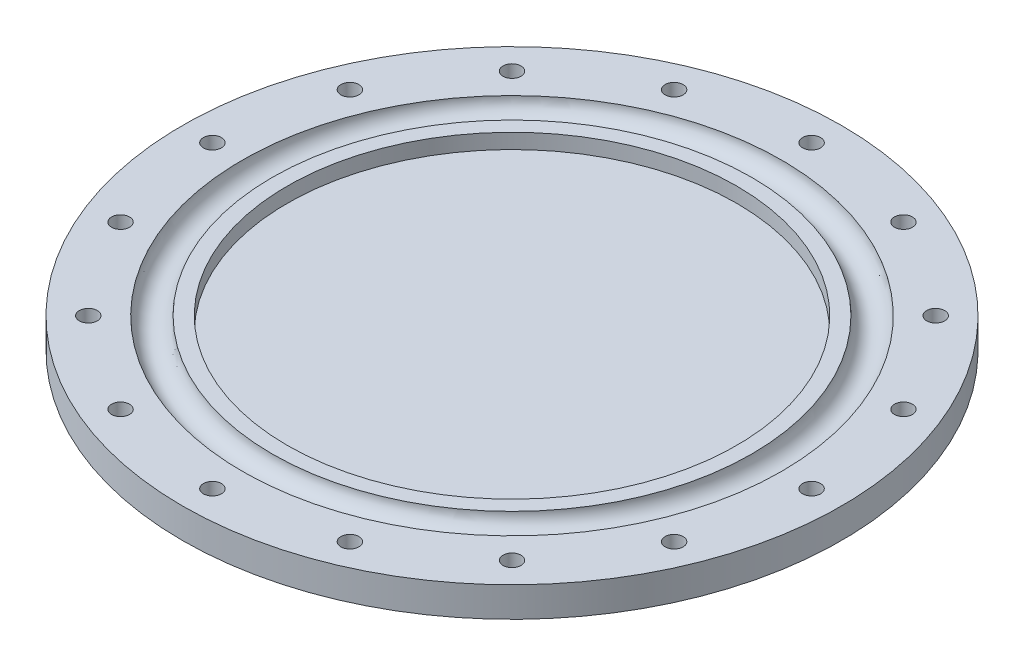
SolidWorks part; units mm, degrees
ref_plane "前视基准面" through (0, 0, 0) normal (0, 0, 1) x (1, 0, 0)
ref_plane "上视基准面" through (0, 0, 0) normal (0, 1, 0) x (1, 0, 0)
ref_plane "右视基准面" through (0, 0, 0) normal (1, 0, 0) x (0, 0, -1)
other "Configuration Table"
sketch "草图1" plane through (0, 0, 0) normal (0, 1, 0) x (1, 0, 0)
  circle A0 centre (0, 0) radius 75
  circle A1 centre (0, 0) radius 80
  circle A2 centre (0, 0) radius 90
  circle A3 centre (0, 0) radius 110
  circle A4 centre (0, 100) radius 3
  circle A5 centre (38.2683, 92.388) radius 3
  circle A6 centre (70.7107, 70.7107) radius 3
  circle A7 centre (92.388, 38.2683) radius 3
  circle A8 centre (100, 0) radius 3
  circle A9 centre (92.388, -38.2683) radius 3
  circle A10 centre (70.7107, -70.7107) radius 3
  circle A11 centre (38.2683, -92.388) radius 3
  circle A12 centre (0, -100) radius 3
  circle A13 centre (-38.2683, -92.388) radius 3
  circle A14 centre (-70.7107, -70.7107) radius 3
  circle A15 centre (-92.388, -38.2683) radius 3
  circle A16 centre (-100, 0) radius 3
  circle A17 centre (-92.388, 38.2683) radius 3
  circle A18 centre (-70.7107, 70.7107) radius 3
  circle A19 centre (-38.2683, 92.388) radius 3
  point P40 (0, 0)
  dimension "D1" = 150
  dimension "D2" = 160
  dimension "D3" = 180
  dimension "D4" = 220
  dimension "D5" = 6
  dimension "D6" = 100
  dimension "D7" = 16
extrude "凸台-拉伸1" add sketch "草图1" along normal blind 10 contours A3 A19 A18 A17 A16 A15 A14 A13 A12 A11 A10 A9 A8 A7 A6 A5 A4 A2 | A1 A0 region at (-77.7373, 0, 0) region at (-106.8887, 0, 0)
extrude "凸台-拉伸2" add sketch "草图1<3>" along normal blind 5 contours A2 A1 | A0 region at (0, 0, 0) region at (-87.4544, 0, 0)
sketch "草图1<3>" plane through (0, 0, 0) normal (0, 1, 0) x (1, 0, 0) same geometry as "草图1"
ref_plane "基准面1" through (0, 5, 0) normal (0, 1, 0) x (1, 0, 0)
sketch "草图2" plane through (0, 5, 0) normal (0, 1, 0) x (1, 0, 0)
  circle A0 centre (0, 0) radius 80
  circle A1 centre (0, 0) radius 90
  dimension "D1" = 160
  dimension "D2" = 180
sketch "草图4" plane through (0, 0, 0) normal (0, 0, 1) x (1, 0, 0)
  line L0 (90, 10) -> (80, 10)
  line L1 (90, 10) -> (-90, 10) construction
  line L2 (95.388, 10) -> (89.388, 10) construction
  line L3 (80, 10) -> (-80, 10) construction
  arc A0 (80, 10) -> (90, 10) centre (85, 10) ccw
ref_plane "基准面2" through (0, 5, 0) normal (0, 1, 0) x (1, 0, 0)
sketch "草图5" plane through (0, 5, 0) normal (0, 1, 0) x (1, 0, 0)
  circle A0 centre (0, 0) radius 85
  dimension "D1" = 170
extrude "凸台-拉伸4" add sketch "草图2" along normal blind 5
sweep "切除-扫描1" cut profiles "草图4" path "草图5"
